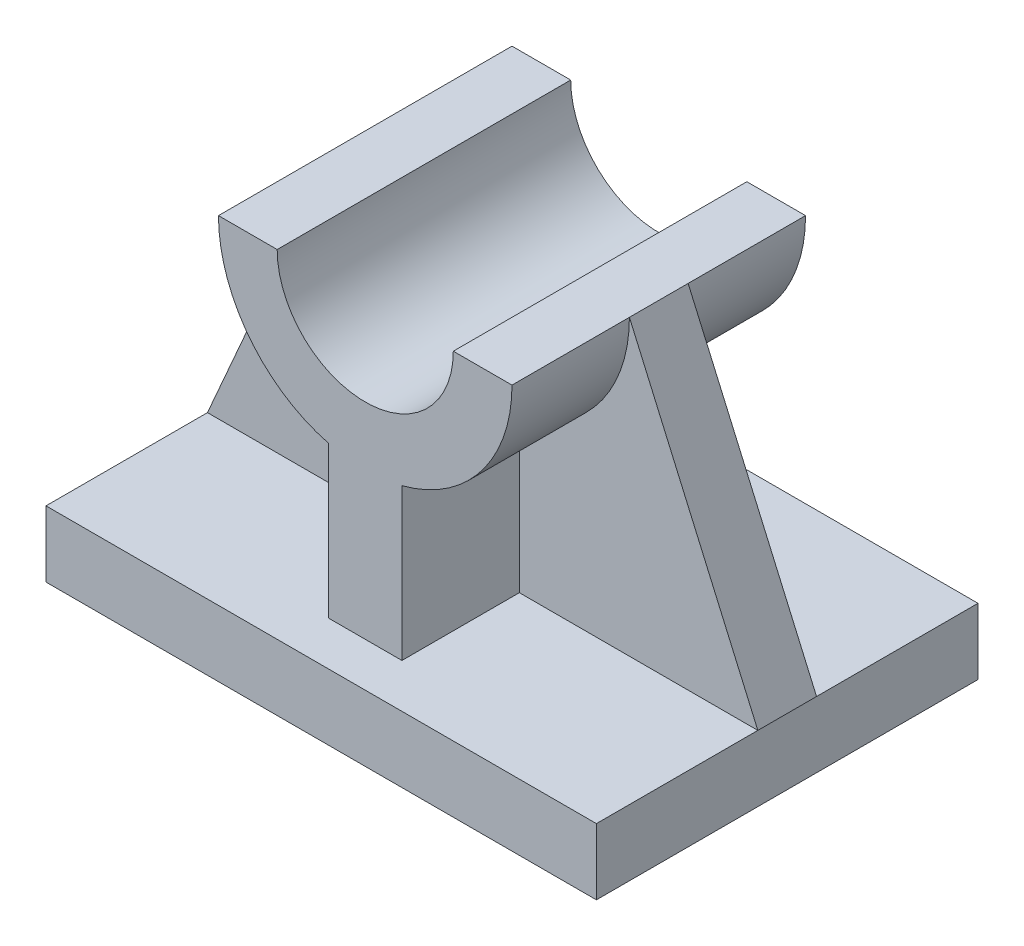
SolidWorks part; units mm, degrees
ref_plane "Front Plane" through (0, 0, 0) normal (0, 0, 1) x (1, 0, 0)
ref_plane "Top Plane" through (0, 0, 0) normal (0, 1, 0) x (1, 0, 0)
ref_plane "Right Plane" through (0, 0, 0) normal (1, 0, 0) x (0, 0, -1)
sketch "Sketch2" plane through (0, 0, 0) normal (0, 0, 1) x (1, 0, 0)
  line L0 (-20, 0) -> (-12, 0)
  line L1 (-5, -19.3649) -> (-5, -40)
  line L2 (-37.5, -40) -> (37.5, -40)
  line L3 (-37.5, -40) -> (-37.5, -49)
  line L4 (-37.5, -49) -> (37.5, -49)
  line L5 (37.5, -40) -> (37.5, -49)
  line L6 (-37.5, -40) -> (37.5, -49) construction
  line L7 (-37.5, -49) -> (37.5, -40) construction
  line L8 (5, -19.3649) -> (5, -40)
  line L9 (0, -44.5) -> (0, 0) construction
  line L10 (0, 0) -> (0, -44.5) construction
  line L11 (-20, 0) -> (-37.5, -40)
  line L12 (20, 0) -> (37.5, -40)
  line L13 (12, 0) -> (20, 0)
  arc A0 (-20, 0) -> (-5, -19.3649) centre (0, 0) ccw
  arc A1 (-12, 0) -> (12, 0) centre (0, 0) ccw
  arc A2 (5, -19.3649) -> (20, 0) centre (0, 0) ccw
  point P5 (0, -44.5)
  dimension "D1" = 40
  dimension "D2" = 8
  dimension "D3" = 75
  dimension "D4" = 9
  dimension "D5" = 40
  dimension "D6" = 10
extrude "Boss-Extrude1" add sketch "Sketch2" along normal mid plane 52 contours L5 L2 L3 L4 region at (0, -44.5, 0)
extrude "Boss-Extrude2" add sketch "Sketch2<4>" along normal mid plane 40 contours L8 A2 L13 A1 L0 A0 L1 L2 region at (0, -16.9191, 0)
sketch "Sketch2<4>" plane through (0, 0, 0) normal (0, 0, 1) x (1, 0, 0) same geometry as "Sketch2"
extrude "Boss-Extrude3" add sketch "Sketch2<5>" along normal mid plane 8 contours A2 L8 L2 L12 | A0 L11 L2 L1 region at (-19.2178, -26.7367, 0) region at (19.2178, -26.7367, 0)
sketch "Sketch2<5>" plane through (0, 0, 0) normal (0, 0, 1) x (1, 0, 0) same geometry as "Sketch2"
